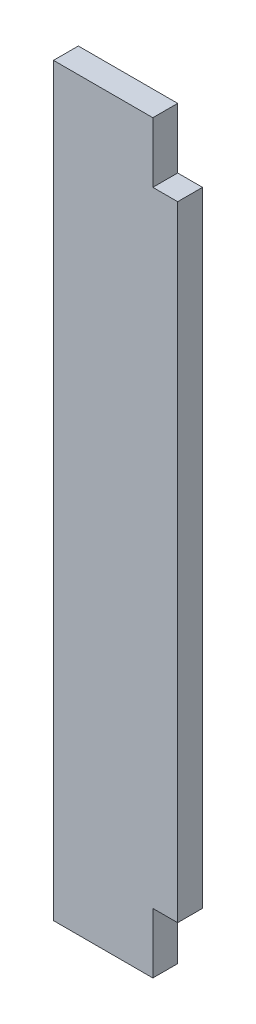
SolidWorks part; units mm, degrees
material "Pine"
ref_plane "Front Plane" through (0, 0, 0) normal (0, 0, 1) x (1, 0, 0)
ref_plane "Top Plane" through (0, 0, 0) normal (0, 1, 0) x (1, 0, 0)
ref_plane "Right Plane" through (0, 0, 0) normal (1, 0, 0) x (0, 0, -1)
sketch "Sketch1" plane through (0, 0, 0) normal (0, 0, 1) x (1, 0, 0)
  line L0 (8932.6508, -5243.5125) -> (10226.1458, -5243.5125)
  line L1 (9086.3208, -4722.0918) -> (10222.9708, -4853.7812)
  line L2 (8914.8708, -6342.0625) -> (10197.5708, -6342.0625)
  line L3 (8914.8708, -5808.6625) -> (10197.5708, -5808.6625)
  line L4 (8919.6333, -5253.0375) -> (10218.2083, -5253.0375)
  line L5 (9134.2633, -4656.1375) -> (9134.2633, -4638.3575)
  line L6 (9091.0833, -4638.3575) -> (9134.2633, -4638.3575)
  line L7 (9091.0833, -4567.2375) -> (9091.0833, -4638.3575)
  line L8 (9134.2633, -4656.1375) -> (9581.3033, -4656.1375)
  line L9 (9091.0833, -4567.2375) -> (9624.4833, -4567.2375)
  line L10 (9581.3033, -4656.1375) -> (9581.3033, -4638.3575)
  line L11 (9581.3033, -4638.3575) -> (9624.4833, -4638.3575)
  line L12 (9624.4833, -4567.2375) -> (9624.4833, -4638.3575)
  line L13 (8932.6508, -5225.7325) -> (9344.9775, -5225.7325)
  line L14 (8932.6508, -5256.2125) -> (8932.6508, -5243.5125)
  line L15 (8911.6958, -5256.2125) -> (8932.6508, -5256.2125)
  line L16 (8914.8708, -4722.0918) -> (9086.3208, -4722.0918)
  line L17 (8911.6958, -4715.5913) -> (8932.6508, -4715.5913)
  line L18 (8914.8708, -6342.0625) -> (8914.8708, -5808.6625)
  line L19 (12082.9917, -4722.0918) -> (10946.3417, -4853.7812)
  line L20 (12236.6617, -5243.5125) -> (10943.1667, -5243.5125)
  line L21 (10951.1042, -5253.0375) -> (12249.6792, -5253.0375)
  line L22 (10838.3917, -5656.2625) -> (11308.2917, -5656.2625)
  line L23 (10838.3917, -5719.7625) -> (11308.2917, -5719.7625)
  line L24 (10838.3917, -5742.5368) -> (11308.2917, -5742.5368)
  line L25 (10806.6417, -6342.0625) -> (11340.0417, -6342.0625)
  line L26 (10803.4667, -6335.7125) -> (11343.2167, -6335.7125)
  line L27 (10803.4667, -6317.9325) -> (11343.2167, -6317.9325)
  line L28 (10943.1667, -5225.7325) -> (11376.4483, -5225.7325)
  line L29 (11506.7292, -4754.5625) -> (10806.6417, -4827.5875)
  line L30 (11506.7292, -4567.2375) -> (11506.7292, -4754.5625)
  line L31 (10806.6417, -4567.2375) -> (10806.6417, -4827.5875)
  line L32 (10806.6417, -4567.2375) -> (11506.7292, -4567.2375)
  line L33 (10235.6708, -6329.3625) -> (10245.1958, -6329.3625)
  line L34 (10245.1958, -6329.3625) -> (10254.7208, -6278.5625)
  line L35 (10302.3458, -6329.3625) -> (10311.8708, -6278.5625)
  line L36 (10302.3458, -6329.3625) -> (10292.8208, -6329.3625)
  line L37 (10245.1958, -5821.3625) -> (10254.7208, -5872.1625)
  line L38 (10235.6708, -5821.3625) -> (10245.1958, -5821.3625)
  line L39 (10292.8208, -5821.3625) -> (10302.3458, -5821.3625)
  line L40 (10302.3458, -5821.3625) -> (10311.8708, -5872.1625)
  line L41 (10235.6708, -5821.3625) -> (10235.6708, -6329.3625)
  line L42 (10254.7208, -5872.1625) -> (10254.7208, -6278.5625)
  line L43 (10311.8708, -5872.1625) -> (10311.8708, -6278.5625)
  line L44 (10292.8208, -5821.3625) -> (10292.8208, -6329.3625)
  line L45 (8932.6508, -5225.7325) -> (8932.6508, -4715.5913)
  line L46 (8911.6958, -4715.5913) -> (8911.6958, -5256.2125)
  line L47 (8914.8708, -5248.275) -> (8914.8708, -4722.0918)
  line L48 (8919.6333, -5253.0375) -> (8914.8708, -5248.275)
  line L49 (8914.8708, -5145.0875) -> (8937.426, -5145.0875)
  line L50 (8914.8708, -5202.2375) -> (8937.426, -5202.2375)
  line L51 (10838.3917, -5656.2625) -> (10838.3917, -5719.7625)
  line L52 (10832.0417, -5736.1868) -> (10856.1717, -5736.1868)
  line L53 (10806.6417, -6342.0625) -> (10806.6417, -5818.7368)
  line L54 (10832.0417, -5649.9125) -> (10856.1717, -5649.9125)
  line L55 (10832.0417, -5726.1125) -> (10856.1717, -5726.1125)
  line L56 (10806.6417, -5818.7368) -> (10833.9015, -5818.7368)
  line L57 (10832.0417, -5806.0442) -> (10851.6815, -5806.0442)
  line L58 (10856.1717, -5801.5541) -> (10856.1717, -5736.1868)
  line L59 (10838.3917, -5814.2467) -> (10838.3917, -5742.5368)
  line L60 (10832.0417, -5806.0442) -> (10832.0417, -5736.1868)
  line L61 (10803.4667, -6317.9325) -> (10803.4667, -6335.7125)
  line L62 (10197.5708, -5808.6625) -> (10197.5708, -6342.0625)
  line L63 (9762.3842, -6348.4125) -> (9762.3842, -5802.3125)
  line L64 (9780.1642, -6348.4125) -> (9762.3842, -6348.4125)
  line L65 (9780.1642, -5802.3125) -> (9780.1642, -6348.4125)
  line L66 (9762.3842, -5802.3125) -> (9780.1642, -5802.3125)
  line L67 (9332.2775, -6348.4125) -> (9332.2775, -5802.3125)
  line L68 (9332.2775, -6348.4125) -> (9350.0575, -6348.4125)
  line L69 (9350.0575, -5802.3125) -> (9350.0575, -6348.4125)
  line L70 (9332.2775, -5802.3125) -> (9350.0575, -5802.3125)
  line L71 (9993.8374, -6061.075) -> (9993.8374, -6045.2418)
  line L72 (9998.5999, -6065.8375) -> (10014.4331, -6065.8375)
  line L73 (9998.5999, -6084.8875) -> (10014.4331, -6084.8875)
  line L74 (9993.8374, -6105.4832) -> (9993.8374, -6089.65)
  line L75 (9974.7874, -6105.4832) -> (9974.7874, -6089.65)
  line L76 (9954.1917, -6084.8875) -> (9970.0249, -6084.8875)
  line L77 (9974.7874, -6061.075) -> (9974.7874, -6045.2418)
  line L78 (9954.1917, -6065.8375) -> (9970.0249, -6065.8375)
  line L79 (10793.9417, -6237.2875) -> (10816.4969, -6237.2875)
  line L80 (10793.9417, -6294.4375) -> (10816.4969, -6294.4375)
  line L81 (10856.1717, -5649.9125) -> (10856.1717, -5726.1125)
  line L82 (10832.0417, -5726.1125) -> (10832.0417, -5649.9125)
  line L83 (10226.1458, -5225.7325) -> (10226.1458, -5243.5125)
  line L84 (10205.1908, -5257.8) -> (10205.1908, -4844.2499)
  line L85 (10230.9083, -4844.2499) -> (10230.9083, -5257.8)
  line L86 (10205.1908, -5257.8) -> (10230.9083, -5257.8)
  line L87 (10205.1908, -4844.2499) -> (10230.9083, -4844.2499)
  line L88 (10946.3417, -5176.8375) -> (10968.8969, -5176.8375)
  line L89 (9349.4676, -5141.9125) -> (9358.2674, -5141.9125)
  line L90 (10946.3417, -5119.6875) -> (10968.8969, -5119.6875)
  line L91 (9929.011, -4660.9635) -> (10066.0807, -4660.9635)
  line L92 (9929.011, -4678.7435) -> (10066.0807, -4678.7435)
  line L93 (10943.1667, -5225.7325) -> (10943.1667, -5243.5125)
  line L94 (10946.3417, -5248.275) -> (10951.1042, -5253.0375)
  line L95 (10946.3417, -5257.8063) -> (10946.3417, -4849.0188)
  line L96 (10964.1217, -5257.8) -> (10964.1217, -4844.2499)
  line L97 (10938.4042, -4844.2499) -> (10938.4042, -5257.8)
  line L98 (10938.4042, -5257.8) -> (10964.1217, -5257.8)
  line L99 (10964.1217, -4844.2499) -> (10938.4042, -4844.2499)
  line L100 (10344.8908, -4560.8875) -> (10369.0208, -4560.8875)
  line L101 (10344.8908, -4560.8875) -> (10369.0208, -4560.8875)
  line L102 (10800.2917, -4560.8875) -> (10824.4217, -4560.8875)
  line L103 (10200.4156, -5119.6875) -> (10222.9708, -5119.6875)
  line L104 (10200.4156, -5176.8375) -> (10222.9708, -5176.8375)
  line L105 (9344.9775, -5146.4026) -> (9344.9775, -5225.7325)
  line L106 (10344.8908, -4560.8875) -> (10344.8908, -4833.9375)
  line L107 (9792.8642, -5225.7325) -> (9792.8642, -5146.4026)
  line L108 (9362.7575, -5225.7325) -> (9775.0842, -5225.7325)
  line L109 (9680.3633, -4761.8396) -> (9680.3633, -4559.9604)
  line L110 (9656.2333, -4559.9604) -> (9680.3633, -4559.9604)
  line L111 (9656.2333, -4761.8396) -> (9680.3633, -4761.8396)
  line L112 (9656.2333, -4761.8396) -> (9656.2333, -4559.9604)
  line L113 (9779.5743, -5141.9125) -> (9788.374, -5141.9125)
  line L114 (10070.5708, -4665.4536) -> (10070.5708, -4674.2534)
  line L115 (9924.5208, -4674.2534) -> (9924.5208, -4665.4536)
  line L116 (12127.4417, -6188.3925) -> (12205.5015, -6188.3925)
  line L117 (12209.9917, -6170.6125) -> (12209.9917, -6183.9024)
  line L118 (9792.8642, -5225.7325) -> (10226.1458, -5225.7325)
  line L119 (9662.5833, -4754.5625) -> (10362.6708, -4827.5875)
  line L120 (9662.5833, -4567.2375) -> (9662.5833, -4754.5625)
  line L121 (10362.6708, -4567.2375) -> (10362.6708, -4827.5875)
  line L122 (9662.5833, -4567.2375) -> (10362.6708, -4567.2375)
  line L123 (10824.4217, -4833.9375) -> (10800.2917, -4833.9375)
  line L124 (10800.2917, -4833.9375) -> (10800.2917, -4560.8875)
  line L125 (10824.4217, -4560.8875) -> (10824.4217, -4833.9375)
  line L126 (10344.8908, -4833.9375) -> (10369.0208, -4833.9375)
  line L127 (10369.0208, -4833.9375) -> (10369.0208, -4560.8875)
  line L128 (10222.9708, -5248.275) -> (10218.2083, -5253.0375)
  line L129 (10222.9708, -5257.8063) -> (10222.9708, -4849.0188)
  line L130 (11734.6544, -5701.375) -> (11739.2301, -5701.375)
  line L131 (9362.7575, -5225.7325) -> (9362.7575, -5146.4026)
  line L132 (9775.0842, -5146.4026) -> (9775.0842, -5225.7325)
  line L133 (11761.3864, -5701.375) -> (11756.8282, -5701.375)
  line L134 (11734.6544, -5693.755) -> (11739.2301, -5693.755)
  line L135 (11761.4039, -5693.755) -> (11756.8282, -5693.755)
  line L136 (11734.6544, -5701.375) -> (11739.2301, -5701.375)
  line L137 (11744.3462, -5721.3024) -> (11744.3462, -5706.4179)
  line L138 (11751.7122, -5721.3024) -> (11751.7122, -5706.4179)
  line L139 (11740.0917, -6170.6125) -> (11740.0917, -6183.9024)
  line L140 (11689.2917, -6188.3925) -> (11822.6417, -6188.3925)
  line L141 (11689.2917, -6348.4093) -> (11689.2917, -6164.2657)
  line L142 (11689.2917, -6164.2657) -> (11746.4417, -6164.2657)
  line L143 (11746.4417, -6164.2657) -> (11746.4417, -6188.3925)
  line L144 (11689.2917, -6164.2657) -> (11746.4417, -6164.2657)
  line L145 (11340.0417, -5818.7368) -> (11340.0417, -6342.0625)
  line L146 (11290.5117, -5726.1125) -> (11314.6417, -5726.1125)
  line L147 (11290.5117, -5649.9125) -> (11290.5117, -5726.1125)
  line L148 (11340.0417, -5818.7368) -> (11312.7818, -5818.7368)
  line L149 (11314.6417, -5806.0442) -> (11295.0018, -5806.0442)
  line L150 (11290.5117, -5801.5541) -> (11290.5117, -5736.1868)
  line L151 (11308.2917, -5814.2467) -> (11308.2917, -5742.5368)
  line L152 (11314.6417, -5806.0442) -> (11314.6417, -5736.1868)
  line L153 (11290.5117, -5736.1868) -> (11314.6417, -5736.1868)
  line L154 (11848.0417, -6267.1325) -> (11962.3417, -6267.1325)
  line L155 (11962.3417, -6267.1325) -> (11962.3417, -6203.6325)
  line L156 (11343.2167, -6317.9325) -> (11343.2167, -6335.7125)
  line L157 (11365.4417, -5656.2625) -> (11365.4417, -5719.7625)
  line L158 (11365.4417, -5656.2625) -> (11479.7417, -5656.2625)
  line L159 (11778.1917, -6071.3937) -> (11802.3217, -6071.3937)
  line L160 (11314.6417, -5726.1125) -> (11314.6417, -5649.9125)
  line L161 (11314.6417, -5649.9125) -> (11290.5117, -5649.9125)
  line L162 (11308.2917, -5719.7625) -> (11308.2917, -5656.2625)
  line L163 (11689.2917, -6348.4093) -> (11713.4217, -6348.4093)
  line L164 (12203.6417, -6164.2657) -> (12260.7917, -6164.2657)
  line L165 (11713.4217, -6348.4093) -> (11713.4217, -6164.2657)
  line L166 (11695.6417, -6342.0625) -> (11695.6417, -6170.6125)
  line L167 (11695.6417, -6048.5337) -> (11699.4517, -6052.3437)
  line L168 (11822.6417, -6292.5325) -> (11822.6417, -6188.3925)
  line L169 (11695.6417, -6342.0625) -> (11695.6417, -6170.6125)
  line L170 (11848.0417, -6203.6325) -> (11962.3417, -6203.6325)
  line L171 (11848.0417, -6203.6325) -> (11848.0417, -6267.1325)
  line L172 (11987.7417, -6267.1325) -> (11987.7417, -6203.6325)
  line L173 (11784.5417, -6077.7437) -> (11784.5417, -6141.2438)
  line L174 (11517.8417, -5656.2625) -> (11632.1417, -5656.2625)
  line L175 (11632.1417, -5656.2625) -> (11632.1417, -5719.7625)
  line L176 (11632.1417, -5719.7625) -> (11517.8417, -5719.7625)
  line L177 (11517.8417, -5719.7625) -> (11517.8417, -5656.2625)
  line L178 (11692.4667, -6028.2137) -> (11692.4667, -6045.9937)
  line L179 (11695.6417, -5979.3188) -> (11718.1969, -5979.3188)
  line L180 (11695.6417, -5922.1687) -> (11718.1969, -5922.1687)
  line L181 (11821.0415, -5722.9375) -> (11821.0415, -5943.6)
  line L182 (11687.7042, -5651.5) -> (11701.9917, -5651.5)
  line L183 (11687.7042, -5651.5) -> (11687.7042, -6055.5251)
  line L184 (11687.7042, -6055.5251) -> (11701.9917, -6055.5251)
  line L185 (11701.9917, -6055.5251) -> (11701.9917, -5651.5)
  line L186 (11695.6417, -6055.2013) -> (11695.6417, -5649.595)
  line L187 (11695.6417, -5656.2625) -> (11695.6417, -6048.5337)
  line L188 (11695.6417, -6170.6125) -> (11740.0917, -6170.6125)
  line L189 (12203.6417, -6164.2657) -> (12203.6417, -6188.3925)
  line L190 (12254.4417, -6342.0625) -> (12254.4417, -6170.6125)
  line L191 (12129.0419, -5943.6) -> (12129.0419, -5722.9375)
  line L192 (12254.4417, -6048.5337) -> (12250.6317, -6052.3437)
  line L193 (12257.6167, -6045.9937) -> (12257.6167, -6028.2137)
  line L194 (12248.0917, -5651.5) -> (12262.3792, -5651.5)
  line L195 (12262.3792, -5651.5) -> (12262.3792, -6055.5251)
  line L196 (12262.3792, -6055.5251) -> (12248.0917, -6055.5251)
  line L197 (12248.0917, -6055.5251) -> (12248.0917, -5651.5)
  line L198 (12254.4417, -6141.2438) -> (12254.4417, -6077.7437)
  line L199 (12236.6617, -6164.2657) -> (12260.7917, -6164.2657)
  line L200 (12102.0417, -6267.1325) -> (11987.7417, -6267.1325)
  line L201 (11330.1865, -6237.2875) -> (11352.7417, -6237.2875)
  line L202 (11330.1865, -6294.4375) -> (11352.7417, -6294.4375)
  line L203 (11474.6617, -5851.8425) -> (11492.4417, -5851.8425)
  line L204 (11474.6617, -5808.6625) -> (11474.6617, -5851.8425)
  line L205 (11403.5417, -5808.6625) -> (11474.6617, -5808.6625)
  line L206 (11492.4417, -5851.8425) -> (11492.4417, -6298.8825)
  line L207 (11403.5417, -6342.0625) -> (11403.5417, -5808.6625)
  line L208 (11474.6617, -6298.8825) -> (11492.4417, -6298.8825)
  line L209 (11474.6617, -6342.0625) -> (11474.6617, -6298.8825)
  line L210 (11403.5417, -6342.0625) -> (11474.6617, -6342.0625)
  line L211 (11619.4417, -5851.8425) -> (11601.6617, -5851.8425)
  line L212 (11601.6617, -5808.6625) -> (11601.6617, -5851.8425)
  line L213 (11530.5417, -5808.6625) -> (11601.6617, -5808.6625)
  line L214 (11619.4417, -5851.8425) -> (11619.4417, -6298.8825)
  line L215 (11530.5417, -6342.0625) -> (11530.5417, -5808.6625)
  line L216 (11619.4417, -6298.8825) -> (11601.6617, -6298.8825)
  line L217 (11601.6617, -6342.0625) -> (11601.6617, -6298.8825)
  line L218 (11530.5417, -6342.0625) -> (11601.6617, -6342.0625)
  line L219 (11479.7417, -5719.7625) -> (11479.7417, -5656.2625)
  line L220 (11365.4417, -5719.7625) -> (11479.7417, -5719.7625)
  line L221 (11778.1917, -6147.5937) -> (11802.3217, -6147.5937)
  line L222 (11802.3217, -6071.3937) -> (11802.3217, -6147.5937)
  line L223 (11778.1917, -6147.5937) -> (11778.1917, -6071.3937)
  line L224 (12254.4417, -5922.1687) -> (12231.8865, -5922.1687)
  line L225 (12254.4417, -5979.3188) -> (12231.8865, -5979.3188)
  line L226 (12254.4417, -6055.2013) -> (12254.4417, -5649.595)
  line L227 (12254.4417, -6048.5337) -> (12254.4417, -5656.2625)
  line L228 (11841.6917, -5702.2873) -> (12108.3917, -5702.2873)
  line L229 (11822.6417, -6292.5325) -> (12127.4417, -6292.5325)
  line L230 (12127.4417, -6292.5325) -> (12127.4417, -6188.3925)
  line L231 (12254.4417, -6170.6125) -> (12209.9917, -6170.6125)
  line L232 (11695.6417, -6342.0625) -> (12254.4417, -6342.0625)
  line L233 (12236.6617, -6348.4093) -> (12260.7917, -6348.4093)
  line L234 (12260.7917, -6348.4093) -> (12260.7917, -6164.2657)
  line L235 (12236.6617, -6348.4093) -> (12236.6617, -6164.2657)
  line L236 (12102.0417, -6203.6325) -> (12102.0417, -6267.1325)
  line L237 (11987.7417, -6203.6325) -> (12102.0417, -6203.6325)
  line L238 (12236.6617, -6147.5937) -> (12236.6617, -6071.3937)
  line L239 (12203.6417, -6188.3925) -> (12260.7917, -6188.3925)
  line L240 (11098.7417, -4665.4536) -> (11098.7417, -4674.2534)
  line L241 (11394.2283, -5146.4026) -> (11394.2283, -5225.7325)
  line L242 (11376.4483, -5225.7325) -> (11376.4483, -5146.4026)
  line L243 (11394.2283, -5225.7325) -> (11806.555, -5225.7325)
  line L244 (11841.6917, -5964.2502) -> (12108.3917, -5964.2502)
  line L245 (12236.6617, -6147.5937) -> (12260.7917, -6147.5937)
  line L246 (12236.6617, -5256.2125) -> (12236.6617, -5243.5125)
  line L247 (12260.7917, -6147.5937) -> (12260.7917, -6071.3937)
  line L248 (12260.7917, -6071.3937) -> (12236.6617, -6071.3937)
  line L249 (12254.4417, -6077.7437) -> (11784.5417, -6077.7437)
  line L250 (11784.5417, -6141.2438) -> (12254.4417, -6141.2438)
  line L252 (12254.4417, -5656.2625) -> (11695.6417, -5656.2625)
  line L253 (11699.4517, -6052.3437) -> (12250.6317, -6052.3437)
  line L254 (11692.4667, -6045.9937) -> (12257.6167, -6045.9937)
  line L255 (11692.4667, -6028.2137) -> (12257.6167, -6028.2137)
  line L256 (11824.335, -5146.4026) -> (11824.335, -5225.7325)
  line L257 (11811.0451, -5141.9125) -> (11819.8449, -5141.9125)
  line L258 (11244.7917, -4674.2534) -> (11244.7917, -4665.4536)
  line L259 (11806.555, -5225.7325) -> (11806.555, -5146.4026)
  line L260 (11488.9492, -4761.8396) -> (11488.9492, -4559.9604)
  line L261 (11488.9492, -4559.9604) -> (11513.0792, -4559.9604)
  line L262 (11488.9492, -4761.8396) -> (11513.0792, -4761.8396)
  line L263 (11513.0792, -4761.8396) -> (11513.0792, -4559.9604)
  line L264 (11240.3015, -4660.9635) -> (11103.2318, -4660.9635)
  line L265 (11103.2318, -4678.7435) -> (11240.3015, -4678.7435)
  line L266 (12236.6617, -5225.7325) -> (12236.6617, -4715.5913)
  line L267 (12257.6167, -4715.5913) -> (12257.6167, -5256.2125)
  line L268 (12254.4417, -5248.275) -> (12254.4417, -4722.0918)
  line L269 (12236.6617, -5225.7325) -> (11824.335, -5225.7325)
  line L270 (12035.0492, -4656.1375) -> (12035.0492, -4638.3575)
  line L271 (12078.2292, -4638.3575) -> (12035.0492, -4638.3575)
  line L272 (12078.2292, -4567.2375) -> (12078.2292, -4638.3575)
  line L273 (12035.0492, -4656.1375) -> (11588.0092, -4656.1375)
  line L274 (11544.8292, -4567.2375) -> (12078.2292, -4567.2375)
  line L275 (11588.0092, -4656.1375) -> (11588.0092, -4638.3575)
  line L276 (11544.8292, -4638.3575) -> (11588.0092, -4638.3575)
  line L277 (11544.8292, -4567.2375) -> (11544.8292, -4638.3575)
  line L278 (12249.6792, -5253.0375) -> (12254.4417, -5248.275)
  line L280 (12257.6167, -5256.2125) -> (12236.6617, -5256.2125)
  line L281 (12231.8865, -5145.0875) -> (12254.4417, -5145.0875)
  line L282 (12231.8865, -5202.2375) -> (12254.4417, -5202.2375)
  line L283 (12236.6617, -4715.5913) -> (12257.6167, -4715.5913)
  line L284 (12082.9917, -4722.0918) -> (12254.4417, -4722.0918)
  line L285 (11380.9385, -5141.9125) -> (11389.7382, -5141.9125)
  circle A0 centre (8923.7608, -4778.9042) radius 1.5875
  circle A1 centre (9062.6598, -4736.3765) radius 2.3685
  circle A2 centre (9051.3958, -6281.7375) radius 22.225
  circle A3 centre (9083.1458, -6249.9875) radius 1.5875
  circle A4 centre (9083.1458, -6313.4875) radius 1.5875
  circle A5 centre (9019.6458, -6249.9875) radius 1.5875
  circle A6 centre (9019.6458, -6313.4875) radius 1.5875
  circle A7 centre (8972.3383, -5202.2375) radius 1.5875
  circle A8 centre (8923.7608, -5015.9708) radius 1.5875
  circle A9 centre (8923.7608, -5134.5042) radius 1.5875
  circle A10 centre (9054.5708, -5234.6225) radius 1.5875
  circle A11 centre (8923.7608, -4897.4375) radius 1.5875
  circle A12 centre (8972.3383, -5087.9375) radius 1.5875
  circle A13 centre (8972.3383, -5145.0875) radius 1.5875
  circle A14 centre (10847.2817, -5668.9625) radius 1.5875
  circle A15 centre (10847.2817, -5707.0625) radius 1.5875
  circle A16 centre (10847.2817, -5755.2368) radius 1.5875
  circle A17 centre (10851.4092, -6237.2875) radius 1.5875
  circle A18 centre (10851.4092, -6294.4375) radius 1.5875
  circle A19 centre (10847.2817, -5793.3442) radius 1.5875
  arc A20 (10833.9015, -5818.7368) -> (10838.3917, -5814.2467) centre (10836.1466, -5816.4918) ccw
  arc A21 (10851.6815, -5806.0442) -> (10856.1717, -5801.5541) centre (10853.9266, -5803.7992) ccw
  circle A22 centre (10882.8417, -6040.4375) radius 1.5875
  circle A23 centre (10882.8417, -6218.2375) radius 1.5875
  circle A24 centre (10882.8417, -5862.6375) radius 1.5875
  circle A25 centre (10908.2417, -6326.8225) radius 1.5875
  circle A26 centre (10908.2417, -6326.8225) radius 1.5875
  circle A27 centre (10851.4092, -6180.1375) radius 1.5875
  circle A28 centre (10815.5317, -4783.4231) radius 1.5875
  circle A29 centre (10815.5317, -4696.9488) radius 1.5875
  circle A30 centre (10815.5317, -4610.4746) radius 1.5875
  circle A31 centre (10979.1323, -4867.0082) radius 2.3685
  circle A32 centre (10190.1802, -4867.0082) radius 2.3685
  circle A33 centre (10955.2317, -4929.9812) radius 1.5875
  circle A34 centre (10955.2317, -5031.5812) radius 1.5875
  circle A35 centre (10214.0808, -4929.9812) radius 1.5875
  circle A36 centre (10214.0808, -5031.5812) radius 1.5875
  circle A37 centre (9341.1675, -6265.8625) radius 1.5875
  circle A38 centre (9771.2742, -5884.8625) radius 1.5875
  circle A39 centre (9771.2742, -6138.8625) radius 1.5875
  circle A40 centre (9771.2742, -6011.8625) radius 1.5875
  arc A41 (10036.2287, -6113.8083) -> (10051.3426, -6111.6033) centre (10042.9639, -6107.0732) ccw
  arc A42 (10051.3426, -6111.6033) -> (10051.3426, -6039.1217) centre (9984.3124, -6075.3625) ccw
  arc A43 (10051.3426, -6039.1217) -> (10036.2287, -6036.9167) centre (10042.9639, -6043.6518) ccw
  arc A44 (10034.5851, -6102.5431) -> (10034.5851, -6048.1819) centre (9984.3124, -6075.3625) ccw
  arc A45 (10034.5851, -6102.5431) -> (10036.2287, -6113.8083) centre (10042.9639, -6107.0732) ccw
  arc A46 (10036.2287, -6036.9167) -> (10034.5851, -6048.1819) centre (10042.9639, -6043.6518) ccw
  arc A47 (9945.8666, -6127.2787) -> (9948.0717, -6142.3927) centre (9952.6018, -6134.0139) ccw
  arc A48 (9948.0717, -6142.3927) -> (10020.5532, -6142.3927) centre (9984.3124, -6075.3625) ccw
  arc A49 (10020.5532, -6142.3927) -> (10022.7583, -6127.2787) centre (10016.0231, -6134.0139) ccw
  arc A50 (9957.1319, -6125.6352) -> (10011.493, -6125.6352) centre (9984.3124, -6075.3625) ccw
  arc A51 (9957.1319, -6125.6352) -> (9945.8666, -6127.2787) centre (9952.6018, -6134.0139) ccw
  arc A52 (10022.7583, -6127.2787) -> (10011.493, -6125.6352) centre (10016.0231, -6134.0139) ccw
  arc A53 (9932.3962, -6036.9167) -> (9917.2822, -6039.1217) centre (9925.661, -6043.6518) ccw
  arc A54 (9917.2822, -6039.1217) -> (9917.2822, -6111.6033) centre (9984.3124, -6075.3625) ccw
  arc A55 (9917.2822, -6111.6033) -> (9932.3962, -6113.8083) centre (9925.661, -6107.0732) ccw
  arc A56 (9934.0398, -6048.1819) -> (9934.0398, -6102.5431) centre (9984.3124, -6075.3625) ccw
  arc A57 (9934.0398, -6048.1819) -> (9932.3962, -6036.9167) centre (9925.661, -6043.6518) ccw
  arc A58 (9932.3962, -6113.8083) -> (9934.0398, -6102.5431) centre (9925.661, -6107.0732) ccw
  arc A59 (9945.8666, -6023.4463) -> (9957.1319, -6025.0898) centre (9952.6018, -6016.7111) ccw
  arc A60 (10011.493, -6025.0898) -> (10022.7583, -6023.4463) centre (10016.0231, -6016.7111) ccw
  arc A61 (10011.493, -6025.0898) -> (9957.1319, -6025.0898) centre (9984.3124, -6075.3625) ccw
  arc A62 (9948.0717, -6008.3323) -> (9945.8666, -6023.4463) centre (9952.6018, -6016.7111) ccw
  arc A63 (10020.5532, -6008.3323) -> (9948.0717, -6008.3323) centre (9984.3124, -6075.3625) ccw
  arc A64 (10022.7583, -6023.4463) -> (10020.5532, -6008.3323) centre (10016.0231, -6016.7111) ccw
  arc A65 (10005.0943, -6187.7574) -> (10096.7073, -6096.1443) centre (9984.3124, -6075.3625) ccw
  arc A66 (9993.8374, -6178.3911) -> (10005.0943, -6187.7574) centre (10003.3624, -6178.3911) ccw
  arc A67 (10001.6306, -6169.0249) -> (10077.9748, -6092.6807) centre (9984.3124, -6075.3625) ccw
  arc A68 (10087.3411, -6084.8875) -> (10077.9748, -6092.6807) centre (10087.3411, -6094.4125) ccw
  arc A69 (10001.6306, -6169.0249) -> (9993.8374, -6178.3911) centre (10003.3624, -6178.3911) ccw
  arc A70 (9963.5306, -6187.7574) -> (9974.7874, -6178.3911) centre (9965.2624, -6178.3911) ccw
  arc A71 (9871.9176, -6096.1443) -> (9963.5306, -6187.7574) centre (9984.3124, -6075.3625) ccw
  arc A72 (9881.2838, -6084.8875) -> (9871.9176, -6096.1443) centre (9881.2838, -6094.4125) ccw
  arc A73 (9890.65, -6092.6807) -> (9966.9943, -6169.0249) centre (9984.3124, -6075.3625) ccw
  arc A74 (9974.7874, -6178.3911) -> (9966.9943, -6169.0249) centre (9965.2624, -6178.3911) ccw
  arc A75 (9890.65, -6092.6807) -> (9881.2838, -6084.8875) centre (9881.2838, -6094.4125) ccw
  arc A76 (9871.9176, -6054.5807) -> (9881.2838, -6065.8375) centre (9881.2838, -6056.3125) ccw
  arc A77 (9963.5306, -5962.9676) -> (9871.9176, -6054.5807) centre (9984.3124, -6075.3625) ccw
  arc A78 (9974.7874, -5972.3339) -> (9963.5306, -5962.9676) centre (9965.2624, -5972.3339) ccw
  arc A79 (9966.9943, -5981.7001) -> (9890.65, -6058.0443) centre (9984.3124, -6075.3625) ccw
  arc A80 (9881.2838, -6065.8375) -> (9890.65, -6058.0443) centre (9881.2838, -6056.3125) ccw
  arc A81 (9966.9943, -5981.7001) -> (9974.7874, -5972.3339) centre (9965.2624, -5972.3339) ccw
  arc A82 (10077.9748, -6058.0443) -> (10087.3411, -6065.8375) centre (10087.3411, -6056.3125) ccw
  arc A83 (9993.8374, -5972.3339) -> (10001.6306, -5981.7001) centre (10003.3624, -5972.3339) ccw
  arc A84 (10077.9748, -6058.0443) -> (10001.6306, -5981.7001) centre (9984.3124, -6075.3625) ccw
  arc A85 (10087.3411, -6065.8375) -> (10096.7073, -6054.5807) centre (10087.3411, -6056.3125) ccw
  arc A86 (10096.7073, -6054.5807) -> (10005.0943, -5962.9676) centre (9984.3124, -6075.3625) ccw
  arc A87 (10005.0943, -5962.9676) -> (9993.8374, -5972.3339) centre (10003.3624, -5972.3339) ccw
  arc A88 (10014.4331, -6065.8375) -> (10018.7361, -6059.0339) centre (10014.4331, -6061.075) ccw
  arc A89 (10018.7361, -6059.0339) -> (10000.641, -6040.9388) centre (9984.3124, -6075.3625) ccw
  arc A90 (10000.641, -6040.9388) -> (9993.8374, -6045.2418) centre (9998.5999, -6045.2418) ccw
  arc A91 (9993.8374, -6061.075) -> (9998.5999, -6065.8375) centre (9998.5999, -6061.075) ccw
  arc A92 (9993.8374, -6105.4832) -> (10000.641, -6109.7862) centre (9998.5999, -6105.4832) ccw
  arc A93 (10000.641, -6109.7862) -> (10018.7361, -6091.6911) centre (9984.3124, -6075.3625) ccw
  arc A94 (10018.7361, -6091.6911) -> (10014.4331, -6084.8875) centre (10014.4331, -6089.65) ccw
  arc A95 (9998.5999, -6084.8875) -> (9993.8374, -6089.65) centre (9998.5999, -6089.65) ccw
  arc A96 (9954.1917, -6084.8875) -> (9949.8888, -6091.6911) centre (9954.1917, -6089.65) ccw
  arc A97 (9949.8888, -6091.6911) -> (9967.9839, -6109.7862) centre (9984.3124, -6075.3625) ccw
  arc A98 (9967.9839, -6109.7862) -> (9974.7874, -6105.4832) centre (9970.0249, -6105.4832) ccw
  arc A99 (9974.7874, -6089.65) -> (9970.0249, -6084.8875) centre (9970.0249, -6089.65) ccw
  arc A100 (9970.0249, -6065.8375) -> (9974.7874, -6061.075) centre (9970.0249, -6061.075) ccw
  arc A101 (9949.8888, -6059.0339) -> (9954.1917, -6065.8375) centre (9954.1917, -6061.075) ccw
  arc A102 (9967.9839, -6040.9388) -> (9949.8888, -6059.0339) centre (9984.3124, -6075.3625) ccw
  arc A103 (9974.7874, -6045.2418) -> (9967.9839, -6040.9388) centre (9970.0249, -6045.2418) ccw
  arc A104 (10096.7073, -6096.1443) -> (10087.3411, -6084.8875) centre (10087.3411, -6094.4125) ccw
  circle A105 centre (9771.2742, -6265.8625) radius 1.5875
  circle A106 centre (9341.1675, -5884.8625) radius 1.5875
  circle A107 centre (9341.1675, -6138.8625) radius 1.5875
  circle A108 centre (9341.1675, -6011.8625) radius 1.5875
  circle A109 centre (11037.2315, -4887.5494) radius 15.0812
  arc A110 (9349.4676, -5141.9125) -> (9344.9775, -5146.4026) centre (9347.2226, -5144.1576) ccw
  arc A111 (9362.7575, -5146.4026) -> (9358.2674, -5141.9125) centre (9360.5124, -5144.1576) ccw
  circle A112 centre (9946.7458, -4669.8535) radius 1.5875
  arc A113 (9924.5208, -4674.2534) -> (9929.011, -4678.7435) centre (9926.7659, -4676.4984) ccw
  circle A114 centre (11003.8092, -5176.8375) radius 1.5875
  circle A115 centre (11003.8092, -5119.6875) radius 1.5875
  circle A116 centre (10353.7808, -4696.9488) radius 1.5875
  circle A117 centre (10353.7808, -4610.4746) radius 1.5875
  circle A118 centre (10353.7808, -4783.4231) radius 1.5875
  circle A119 centre (11003.8092, -5062.5375) radius 1.5875
  circle A120 centre (9353.8675, -5160.9625) radius 1.5875
  circle A121 centre (9638.7708, -5234.6225) radius 1.5875
  circle A122 centre (9671.4733, -4724.1144) radius 1.5875
  circle A123 centre (9671.4733, -4661.3637) radius 1.5875
  circle A124 centre (9671.4733, -4598.6129) radius 1.5875
  arc A125 (9792.8642, -5146.4026) -> (9788.374, -5141.9125) centre (9790.6191, -5144.1576) ccw
  arc A126 (9779.5743, -5141.9125) -> (9775.0842, -5146.4026) centre (9777.3292, -5144.1576) ccw
  circle A127 centre (10048.3458, -4669.8535) radius 1.5875
  arc A128 (10070.5708, -4665.4536) -> (10066.0807, -4660.9635) centre (10068.3258, -4663.2086) ccw
  arc A129 (10066.0807, -4678.7435) -> (10070.5708, -4674.2534) centre (10068.3258, -4676.4984) ccw
  circle A130 centre (9997.5458, -4669.8535) radius 1.5875
  arc A131 (9929.011, -4660.9635) -> (9924.5208, -4665.4536) centre (9926.7659, -4663.2086) ccw
  circle A132 centre (10132.081, -4887.5494) radius 15.0812
  circle A133 centre (10165.5033, -5176.8375) radius 1.5875
  circle A134 centre (10165.5033, -5119.6875) radius 1.5875
  circle A135 centre (9486.3708, -5234.6225) radius 1.5875
  circle A136 centre (10165.5033, -5062.5375) radius 1.5875
  circle A137 centre (9206.9708, -5234.6225) radius 1.5875
  circle A138 centre (10070.5708, -5234.6225) radius 1.5875
  circle A139 centre (9918.1708, -5234.6225) radius 1.5875
  circle A140 centre (9783.9742, -5160.9625) radius 1.5875
  circle A141 centre (9783.9742, -5193.9825) radius 1.5875
  circle A142 centre (9353.8675, -5193.9825) radius 1.5875
  circle A143 centre (11073.3417, -6326.8225) radius 1.5875
  circle A144 centre (11073.3417, -6326.8225) radius 1.5875
  circle A145 centre (11295.2742, -6180.1375) radius 1.5875
  circle A146 centre (11295.2742, -6294.4375) radius 1.5875
  circle A147 centre (11295.2742, -6237.2875) radius 1.5875
  circle A148 centre (11975.0417, -5692.775) radius 3.4925
  circle A149 centre (11263.8417, -5862.6375) radius 1.5875
  arc A150 (11739.2301, -5701.375) -> (11744.3462, -5706.4179) centre (11748.0292, -5697.565) ccw
  arc A151 (11751.7122, -5706.4179) -> (11756.8282, -5701.375) centre (11748.0292, -5697.565) ccw
  arc A152 (11744.3462, -5721.3024) -> (11751.7122, -5721.3024) centre (11748.0292, -5725.505) ccw
  arc A153 (11734.6544, -5693.755) -> (11724.9787, -5697.565) centre (11730.5667, -5697.565) ccw
  arc A154 (11756.8282, -5693.755) -> (11739.2301, -5693.755) centre (11748.0292, -5697.565) ccw
  arc A155 (11724.9787, -5697.565) -> (11734.6544, -5701.375) centre (11730.5667, -5697.565) ccw
  arc A156 (11761.3864, -5701.375) -> (11771.0797, -5697.565) centre (11765.4842, -5697.565) ccw
  arc A157 (11771.0797, -5697.565) -> (11761.4039, -5693.755) centre (11765.4917, -5697.565) ccw
  arc A158 (11740.0917, -6183.9024) -> (11744.5818, -6188.3925) centre (11742.3367, -6186.1474) ccw
  arc A159 (12205.5015, -6188.3925) -> (12209.9917, -6183.9024) centre (12207.7466, -6186.1474) ccw
  circle A160 centre (11299.4017, -5793.3442) radius 1.5875
  arc A161 (11308.2917, -5814.2467) -> (11312.7818, -5818.7368) centre (11310.5367, -5816.4918) ccw
  arc A162 (11290.5117, -5801.5541) -> (11295.0018, -5806.0442) centre (11292.7567, -5803.7992) ccw
  circle A163 centre (11704.5317, -6314.149) radius 1.5875
  circle A164 centre (11748.9817, -6208.7125) radius 1.5875
  circle A165 centre (11263.8417, -6218.2375) radius 1.5875
  circle A166 centre (11263.8417, -6040.4375) radius 1.5875
  circle A167 centre (11238.4417, -6326.8225) radius 1.5875
  circle A168 centre (11238.4417, -6326.8225) radius 1.5875
  circle A169 centre (11299.4017, -5668.9625) radius 1.5875
  circle A170 centre (11299.4017, -5707.0625) radius 1.5875
  circle A171 centre (11726.7567, -6179.5025) radius 1.5875
  circle A172 centre (11704.5317, -6199.3198) radius 1.5875
  circle A173 centre (11748.9817, -6272.2125) radius 1.5875
  circle A174 centre (11704.5317, -6256.7344) radius 1.5875
  circle A175 centre (11299.4017, -5755.2368) radius 1.5875
  circle A176 centre (11913.4467, -6301.4225) radius 1.5875
  circle A177 centre (11790.2567, -6301.4225) radius 1.5875
  circle A178 centre (11793.4317, -6128.5437) radius 1.5875
  circle A179 centre (11753.1092, -5865.0188) radius 1.5875
  circle A180 centre (11809.9417, -6037.1038) radius 1.5875
  circle A181 centre (11809.9417, -6037.1038) radius 1.5875
  circle A182 centre (11753.1092, -5922.1687) radius 1.5875
  circle A183 centre (11975.0417, -5973.7625) radius 3.4925
  circle A184 centre (11975.0417, -6037.1038) radius 1.5875
  circle A185 centre (11753.1092, -5979.3188) radius 1.5875
  circle A186 centre (11975.0417, -6037.1038) radius 1.5875
  arc A187 (11841.6917, -5702.2873) -> (11821.0415, -5722.9375) centre (11841.6917, -5722.9375) ccw
  circle A188 centre (11811.5292, -5833.2687) radius 3.4925
  arc A189 (11821.0415, -5943.6) -> (11841.6917, -5964.2502) centre (11841.6917, -5943.6) ccw
  circle A190 centre (12196.9742, -5865.0188) radius 1.5875
  arc A191 (12129.0419, -5722.9375) -> (12108.3917, -5702.2873) centre (12108.3917, -5722.9375) ccw
  circle A192 centre (12036.6367, -6301.4225) radius 1.5875
  circle A193 centre (12159.8267, -6301.4225) radius 1.5875
  circle A194 centre (12138.5542, -5833.2687) radius 3.4925
  circle A195 centre (12197.2917, -5761.0375) radius 15.0812
  circle A196 centre (11793.4317, -6090.4437) radius 1.5875
  circle A197 centre (12196.9742, -5922.1687) radius 1.5875
  arc A198 (12108.3917, -5964.2502) -> (12129.0419, -5943.6) centre (12108.3917, -5943.6) ccw
  circle A199 centre (12196.9742, -5979.3188) radius 1.5875
  circle A200 centre (12201.1017, -6272.2125) radius 1.5875
  circle A201 centre (12245.5517, -6314.149) radius 1.5875
  circle A202 centre (12245.5517, -6256.7344) radius 1.5875
  circle A203 centre (12201.1017, -6208.7125) radius 1.5875
  circle A204 centre (12223.3267, -6179.5025) radius 1.5875
  circle A205 centre (12245.5517, -6199.3198) radius 1.5875
  circle A206 centre (11171.7667, -4669.8535) radius 1.5875
  circle A207 centre (11222.5667, -4669.8535) radius 1.5875
  arc A208 (11240.3015, -4678.7435) -> (11244.7917, -4674.2534) centre (11242.5466, -4676.4984) ccw
  circle A209 centre (11385.3383, -5193.9825) radius 1.5875
  circle A210 centre (12106.6527, -4736.3765) radius 2.3685
  circle A211 centre (12140.1417, -6037.1038) radius 1.5875
  circle A212 centre (12140.1417, -6037.1038) radius 1.5875
  circle A213 centre (12245.5517, -6090.4437) radius 1.5875
  circle A214 centre (12245.5517, -6128.5437) radius 1.5875
  circle A215 centre (11385.3383, -5160.9625) radius 1.5875
  arc A216 (11824.335, -5146.4026) -> (11819.8449, -5141.9125) centre (11822.0899, -5144.1576) ccw
  arc A217 (11811.0451, -5141.9125) -> (11806.555, -5146.4026) centre (11808.8001, -5144.1576) ccw
  circle A218 centre (11815.445, -5193.9825) radius 1.5875
  circle A219 centre (11815.445, -5160.9625) radius 1.5875
  circle A220 centre (11530.5417, -5234.6225) radius 1.5875
  circle A221 centre (11962.3417, -5234.6225) radius 1.5875
  arc A222 (11244.7917, -4665.4536) -> (11240.3015, -4660.9635) centre (11242.5466, -4663.2086) ccw
  circle A223 centre (11682.9417, -5234.6225) radius 1.5875
  circle A224 centre (11497.8392, -4724.1144) radius 1.5875
  circle A225 centre (11497.8392, -4661.3637) radius 1.5875
  circle A226 centre (11497.8392, -4598.6129) radius 1.5875
  circle A227 centre (11120.9667, -4669.8535) radius 1.5875
  arc A228 (11103.2318, -4660.9635) -> (11098.7417, -4665.4536) centre (11100.9867, -4663.2086) ccw
  arc A229 (11098.7417, -4674.2534) -> (11103.2318, -4678.7435) centre (11100.9867, -4676.4984) ccw
  circle A230 centre (12196.9742, -5202.2375) radius 1.5875
  circle A231 centre (12245.5517, -5015.9708) radius 1.5875
  circle A232 centre (12245.5517, -5134.5042) radius 1.5875
  circle A233 centre (12114.7417, -5234.6225) radius 1.5875
  circle A234 centre (12245.5517, -4897.4375) radius 1.5875
  circle A235 centre (12245.5517, -4778.9042) radius 1.5875
  circle A236 centre (12196.9742, -5087.9375) radius 1.5875
  circle A237 centre (12196.9742, -5145.0875) radius 1.5875
  circle A238 centre (11098.7417, -5234.6225) radius 1.5875
  circle A239 centre (11251.1417, -5234.6225) radius 1.5875
  arc A240 (11380.9385, -5141.9125) -> (11376.4483, -5146.4026) centre (11378.6934, -5144.1576) ccw
  arc A241 (11394.2283, -5146.4026) -> (11389.7382, -5141.9125) centre (11391.9833, -5144.1576) ccw
sketch "Sketch2" plane through (0, 0, 0) normal (0, 0, 1) x (1, 0, 0)
  line L0 (11403.5417, -6342.0625) -> (11474.6617, -6342.0625)
  line L1 (11474.6617, -6342.0625) -> (11474.6617, -6298.8825)
  line L2 (11474.6617, -6298.8825) -> (11492.4417, -6298.8825)
  line L3 (11492.4417, -6298.8825) -> (11492.4417, -5851.8425)
  line L4 (11492.4417, -5851.8425) -> (11474.6617, -5851.8425)
  line L5 (11474.6617, -5851.8425) -> (11474.6617, -5808.6625)
  line L6 (11474.6617, -5808.6625) -> (11403.5417, -5808.6625)
  line L7 (11403.5417, -5808.6625) -> (11403.5417, -6342.0625)
extrude "Extrude1" add sketch "Sketch2" against normal blind 17.78
